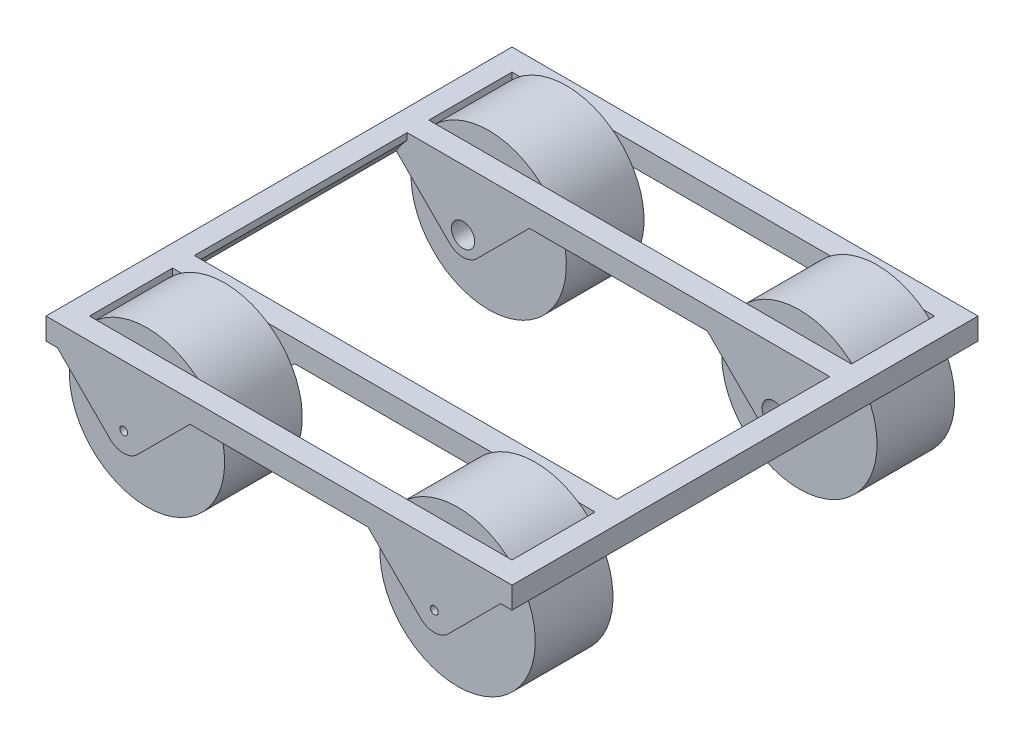
SolidWorks part; units mm, degrees
ref_plane "Front Plane" through (0, 0, 0) normal (0, 0, 1) x (1, 0, 0)
ref_plane "Top Plane" through (0, 0, 0) normal (0, 1, 0) x (1, 0, 0)
ref_plane "Right Plane" through (0, 0, 0) normal (1, 0, 0) x (0, 0, -1)
sketch "Sketch1" plane through (0, 0, 0) normal (0, 0, 1) x (1, 0, 0)
  line L0 (0, 0) -> (-300, 0)
  line L1 (-300, 0) -> (-300, 28)
  line L2 (-300, 28) -> (0, 28)
  line L3 (-272, 0) -> (-272, 28)
  line L4 (-217.6777, -67.6777) -> (-285.3553, 0)
  line L5 (-114.6447, 0) -> (-182.3223, -67.6777)
  line L6 (0, 28) -> (0, 0)
  circle A0 centre (-200, -50) radius 100
  circle A1 centre (-200, -50) radius 5
  circle A2 centre (-200, -50) radius 15
  circle A3 centre (-200, -50) radius 25
  dimension "D1" = 200
  dimension "D2" = 10
  dimension "D3" = 30
  dimension "D4" = 50
  dimension "D7" = 100
  dimension "D5" = 50
  dimension "D6" = 300
  dimension "D8" = 28
  dimension "D9" = 28
  dimension "D10" = 45
  dimension "D11" = 45
extrude "Boss-Extrude1" add sketch "Sketch1" against normal blind 28 from offset 300 contours L0 A0 L2 L3 | A0 L2 L3 | L3 A0 L0 | A0 L0 L6 L2 | A0 L3 L2 L1 L0 | A3 L5 L0 L4 | A3 A2 | A2 A1 region at (-200, -19.0293, 0) region at (-197.118, 13.5168, 0) region at (-277.0758, 6.7318, 0) region at (-62.141, 14.447, 0) region at (-200, -74.2929, 0) region at (-288.1745, 15.771, 0) region at (-268.927, 25.1938, 0) region at (-214.5757, -50, 0)
extrude "Boss-Extrude2" add sketch "Sketch1<4>" along normal blind 300 contours A0 L3 L2 L1 L0 region at (-288.1745, 15.771, 0)
sketch "Sketch1<4>" plane through (0, 0, 0) normal (0, 0, 1) x (1, 0, 0) same geometry as "Sketch1"
extrude "Boss-Extrude3" add sketch "Sketch1<5>" against normal blind 100 from offset 270 contours L2 A0 | L0 A0 L2 L3 | A3 L5 L0 L4 | A3 L4 L0 A0 L5 | L3 A0 L0 region at (-200, -19.0293, 0) region at (-197.118, 13.5168, 0) region at (-200, -82.7593, 0) region at (-277.0758, 6.7318, 0) region at (-200, 36.8886, 0)
sketch "Sketch1<5>" plane through (0, 0, 0) normal (0, 0, 1) x (1, 0, 0) same geometry as "Sketch1"
extrude "Boss-Extrude4" add sketch "Sketch1<6>" against normal blind 28 from offset 165 contours A0 L0 L6 L2 | L0 A0 L2 L3 | A3 L5 L0 L4 | A3 A2 | A0 L2 L3 | A0 L3 L2 L1 L0 | L3 A0 L0 region at (-200, -19.0293, 0) region at (-197.118, 13.5168, 0) region at (-277.0758, 6.7318, 0) region at (-62.141, 14.447, 0) region at (-200, -74.2929, 0) region at (-288.1745, 15.771, 0) region at (-268.927, 25.1938, 0)
sketch "Sketch1<6>" plane through (0, 0, 0) normal (0, 0, 1) x (1, 0, 0) same geometry as "Sketch1"
mirror "Mirror1" about plane through (0, 0, 0) normal (0, 0, 1) of bodies 105
mirror "Mirror2" about plane through (0, 0, 0) normal (1, 0, 0) of bodies 106
